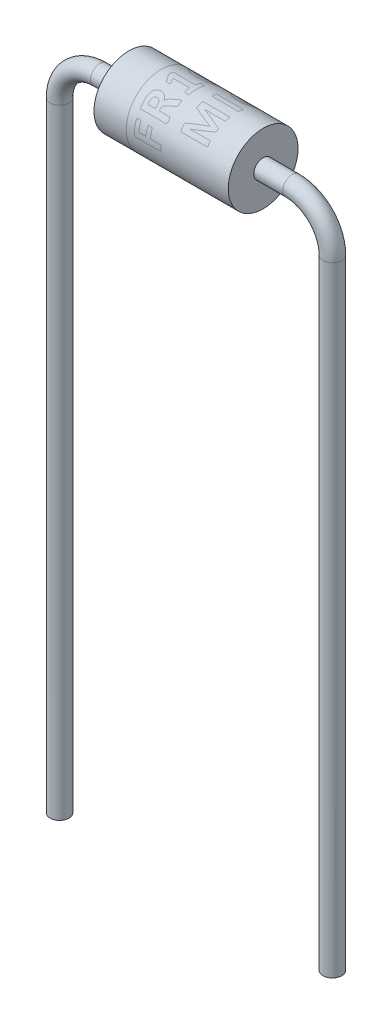
SolidWorks part; units mm, degrees
other "Wire"
other "Cathode Silver Band"
other "Diode"
ref_plane "Front Plane" through (0, 0, 0) normal (0, 0, 1) x (1, 0, 0)
ref_plane "Top Plane" through (0, 0, 0) normal (0, 1, 0) x (1, 0, 0)
ref_plane "Right Plane" through (0, 0, 0) normal (1, 0, 0) x (0, 0, -1)
sketch "Sketch1" plane through (0, 0, 0) normal (1, 0, 0) x (0, 0, -1)
  circle A0 centre (0, 0) radius 1.3
  circle A1 centre (0, 0) radius 0.35
  dimension "D1" = 2.6
  dimension "D2" = 0.7
extrude "Boss-Extrude1" add sketch "Sketch1" along normal mid plane 5
sketch "Sketch2" plane through (-2.5, 0, 0) normal (-1, 0, 0) x (0, 0, 1)
  circle A1 centre (0, 0) radius 1.3 construction
  circle A2 centre (0, 0) radius 1.29
  circle A3 centre (0, 0) radius 1.29
  circle A4 centre (0, 0) radius 1.3
  dimension "D1" = 0.01
extrude "Cut-Extrude1" cut sketch "Sketch2" against normal blind 1.2
sketch "Sketch3" plane through (-1.3, 0, 0) normal (-1, 0, 0) x (0, 0, 1)
  circle A0 centre (0, 0) radius 1.29 construction
  circle A1 centre (0, 0) radius 1.29
  circle A2 centre (0, 0) radius 1.3 construction
  circle A3 centre (0, 0) radius 1.3
extrude "Boss-Extrude2" add sketch "Sketch3" along normal up to surface (1.2 mm away) separate body up to face at (-2.5, 0, -0.35)
ref_plane "Plane1" through (0, 5, 0) normal (0, 1, 0) x (1, 0, 0)
sketch "Sketch4" plane through (0, 5, 0) normal (0, 1, 0) x (1, 0, 0)
  line L0 (0, 7.5) -> (0, -7.5) construction
  line L1 (0, 0) -> (-2.5, 0) construction
  line L2 (-2.5, 1.3) -> (-2.5, -1.3) construction
  line L4 (0, 0) -> (1.5, 0) construction
  line L5 (1.5, 7.5) -> (1.5, -7.5) construction
  text T0 "FR107" font "Calibri" height 1
  text T1 "MIC" font "Corbel" height 1
  dimension "D1" = 2.5
  dimension "D2" = 15
  dimension "D3" = 1.5
wrap "Wrap1" sketch "Sketch4" wrap type scribe source sketch "Sketch4" face at (2.5, 0, -1.3)
sketch "Sketch5" plane through (0, 0, 0) normal (0, 0, 1) x (1, 0, 0)
  line L0 (0, 0) -> (-3.58, 0)
  line L1 (-5.08, -1.5) -> (-5.08, -24.5638)
  line L2 (0, 0) -> (3.58, 0)
  line L3 (5.08, -1.5) -> (5.08, -24.5638)
  arc A0 (-3.58, 0) -> (-5.08, -1.5) centre (-3.58, -1.5) ccw
  arc A1 (3.58, 0) -> (5.08, -1.5) centre (3.58, -1.5) cw
  dimension "D2" = 1.5
  dimension "D3" = 58
  dimension "D1" = 10.16
sketch "Sketch6" plane through (0, 0, 0) normal (1, 0, 0) x (0, 0, -1)
  circle A0 centre (0, 0) radius 0.35
  dimension "D1" = 0.7
sweep "Sweep1" add profiles "Sketch6" path "Sketch5"
